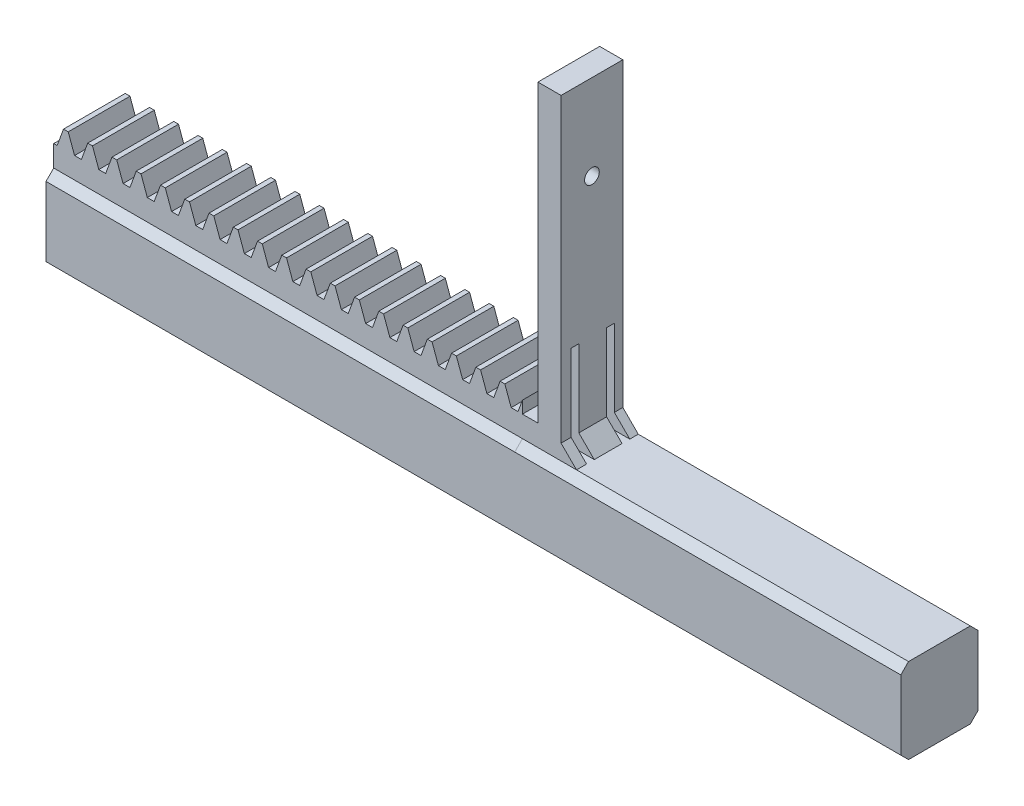
SolidWorks part; units mm, degrees
ref_plane "Front Plane" through (0, 0, 0) normal (0, 0, 1) x (1, 0, 0)
ref_plane "Top Plane" through (0, 0, 0) normal (0, 1, 0) x (1, 0, 0)
ref_plane "Right Plane" through (0, 0, 0) normal (1, 0, 0) x (0, 0, -1)
ref_plane "Plane1" through (0, 0, -3.7928) normal (0, 0, -1) x (-1, 0, 0)
sketch "Sketch1" plane through (0, 0, -3.7928) normal (0, 0, -1) x (-1, 0, 0)
  line L0 (23.517, -6.4086) -> (22.698, -8.6586)
  line L1 (22.698, -8.6586) -> (21.8092, -8.6586)
  line L2 (21.8092, -8.6586) -> (21.2359, -7.0836)
  line L3 (21.2359, -7.0836) -> (21.2359, -12.4086)
  line L4 (21.2359, -12.4086) -> (66.2359, -12.4086)
  line L5 (81.9439, -8.6586) -> (81.9439, -12.4086)
  line L6 (66.6803, -8.6586) -> (65.7915, -8.6586)
  line L7 (65.7915, -8.6586) -> (64.9725, -6.4086)
  line L8 (64.9725, -6.4086) -> (64.3577, -6.4086)
  line L9 (64.3577, -6.4086) -> (63.5387, -8.6586)
  line L10 (63.5387, -8.6586) -> (62.6499, -8.6586)
  line L11 (62.6499, -8.6586) -> (61.8309, -6.4086)
  line L12 (61.8309, -6.4086) -> (61.2161, -6.4086)
  line L13 (61.2161, -6.4086) -> (60.3971, -8.6586)
  line L14 (60.3971, -8.6586) -> (59.5083, -8.6586)
  line L15 (59.5083, -8.6586) -> (58.6893, -6.4086)
  line L16 (58.6893, -6.4086) -> (58.0745, -6.4086)
  line L17 (58.0745, -6.4086) -> (57.2555, -8.6586)
  line L18 (57.2555, -8.6586) -> (56.3667, -8.6586)
  line L19 (56.3667, -8.6586) -> (55.5477, -6.4086)
  line L20 (55.5477, -6.4086) -> (54.9329, -6.4086)
  line L21 (54.9329, -6.4086) -> (54.114, -8.6586)
  line L22 (54.114, -8.6586) -> (53.2251, -8.6586)
  line L23 (53.2251, -8.6586) -> (52.4062, -6.4086)
  line L24 (52.4062, -6.4086) -> (51.7913, -6.4086)
  line L25 (51.7913, -6.4086) -> (50.9724, -8.6586)
  line L26 (50.9724, -8.6586) -> (50.0835, -8.6586)
  line L27 (50.0835, -8.6586) -> (49.2646, -6.4086)
  line L28 (49.2646, -6.4086) -> (48.6497, -6.4086)
  line L29 (48.6497, -6.4086) -> (47.8308, -8.6586)
  line L30 (47.8308, -8.6586) -> (46.9419, -8.6586)
  line L31 (46.9419, -8.6586) -> (46.123, -6.4086)
  line L32 (46.123, -6.4086) -> (45.5081, -6.4086)
  line L33 (45.5081, -6.4086) -> (44.6892, -8.6586)
  line L34 (44.6892, -8.6586) -> (43.8003, -8.6586)
  line L35 (43.8003, -8.6586) -> (42.9814, -6.4086)
  line L36 (42.9814, -6.4086) -> (42.3665, -6.4086)
  line L37 (42.3665, -6.4086) -> (41.5476, -8.6586)
  line L38 (41.5476, -8.6586) -> (40.6587, -8.6586)
  line L39 (40.6587, -8.6586) -> (39.8398, -6.4086)
  line L40 (39.8398, -6.4086) -> (39.2249, -6.4086)
  line L41 (39.2249, -6.4086) -> (38.406, -8.6586)
  line L42 (38.406, -8.6586) -> (37.5171, -8.6586)
  line L43 (37.5171, -8.6586) -> (36.6982, -6.4086)
  line L44 (36.6982, -6.4086) -> (36.0833, -6.4086)
  line L45 (36.0833, -6.4086) -> (35.2644, -8.6586)
  line L46 (35.2644, -8.6586) -> (34.3755, -8.6586)
  line L47 (34.3755, -8.6586) -> (33.5566, -6.4086)
  line L48 (33.5566, -6.4086) -> (32.9417, -6.4086)
  line L49 (32.9417, -6.4086) -> (32.1228, -8.6586)
  line L50 (32.1228, -8.6586) -> (31.2339, -8.6586)
  line L51 (31.2339, -8.6586) -> (30.415, -6.4086)
  line L52 (30.415, -6.4086) -> (29.8001, -6.4086)
  line L53 (29.8001, -6.4086) -> (28.9812, -8.6586)
  line L54 (28.9812, -8.6586) -> (28.0923, -8.6586)
  line L55 (28.0923, -8.6586) -> (27.2734, -6.4086)
  line L56 (27.2734, -6.4086) -> (26.6586, -6.4086)
  line L57 (26.6586, -6.4086) -> (25.8396, -8.6586)
  line L58 (25.8396, -8.6586) -> (24.9508, -8.6586)
  line L59 (24.9508, -8.6586) -> (24.1318, -6.4086)
  line L60 (24.1318, -6.4086) -> (23.517, -6.4086)
  line L61 (81.4994, -8.6586) -> (81.9439, -8.6586)
  line L62 (80.6805, -6.4086) -> (81.4994, -8.6586)
  line L63 (80.0656, -6.4086) -> (80.6805, -6.4086)
  line L64 (79.2467, -8.6586) -> (80.0656, -6.4086)
  line L65 (78.3578, -8.6586) -> (79.2467, -8.6586)
  line L66 (77.5389, -6.4086) -> (78.3578, -8.6586)
  line L67 (76.924, -6.4086) -> (77.5389, -6.4086)
  line L68 (76.1051, -8.6586) -> (76.924, -6.4086)
  line L69 (75.2162, -8.6586) -> (76.1051, -8.6586)
  line L70 (74.3973, -6.4086) -> (75.2162, -8.6586)
  line L71 (73.7824, -6.4086) -> (74.3973, -6.4086)
  line L72 (72.9635, -8.6586) -> (73.7824, -6.4086)
  line L73 (72.0746, -8.6586) -> (72.9635, -8.6586)
  line L74 (71.2557, -6.4086) -> (72.0746, -8.6586)
  line L75 (70.6409, -6.4086) -> (71.2557, -6.4086)
  line L76 (69.8219, -8.6586) -> (70.6409, -6.4086)
  line L77 (68.933, -8.6586) -> (69.8219, -8.6586)
  line L78 (68.1141, -6.4086) -> (68.933, -8.6586)
  line L79 (67.4993, -6.4086) -> (68.1141, -6.4086)
  line L80 (66.6803, -8.6586) -> (67.4993, -6.4086)
  line L81 (66.2359, -12.4086) -> (81.9439, -12.4086)
extrude "Boss-Extrude1" add sketch "Sketch1" against normal blind 8
sketch "Sketch2" plane through (0, -12.4086, 0) normal (0, -1, 0) x (1, 0, 0)
  line L0 (-81.9439, 4.2072) -> (-81.9439, -3.7928) construction
  line L1 (-81.9439, 5.2072) -> (28.7641, 5.2072)
  line L2 (-81.9439, 5.2072) -> (-81.9439, -4.7928)
  line L3 (-81.9439, -4.7928) -> (28.7641, -4.7928)
  line L4 (28.7641, 5.2072) -> (28.7641, -4.7928)
  line L5 (-21.2359, 4.2072) -> (-21.2359, -3.7928) construction
  point P8 (-81.9439, 0.2072)
  dimension "D1" = 10
  dimension "D2" = 50
extrude "Boss-Extrude2" add sketch "Sketch2" along normal blind 10
chamfer "Chamfer1" distance 1 angle 45 1 edges at (-51.5899, -12.4086, 4.2072)
chamfer "Chamfer2" distance 1 angle 45 1 edges at (-51.5899, -12.4086, -3.7928)
sketch "Sketch3" plane through (0, -12.4086, 0) normal (0, 1, 0) x (1, 0, 0)
  line L1 (-21.2359, 3.7928) -> (28.7641, 3.7928)
  line L2 (-21.2359, 3.7928) -> (-21.2359, -4.2072)
  line L3 (-21.2359, -4.2072) -> (28.7641, -4.2072)
  line L4 (28.7641, 3.7928) -> (28.7641, -4.2072)
  line L6 (28.7641, 4.7928) -> (28.7641, -5.2072) construction
  dimension "D1" = 8
extrude "Boss-Extrude3" add sketch "Sketch3" along normal blind 1
chamfer "Chamfer3" distance 1 angle 45 1 edges at (3.7641, -12.4086, 4.2072)
chamfer "Chamfer4" distance 1 angle 45 1 edges at (3.7641, -12.4086, -3.7928)
sketch "Sketch4" plane through (0, -22.4086, 0) normal (0, -1, 0) x (1, 0, 0)
  line L1 (-19.2359, 4.2072) -> (-16.2359, 4.2072)
  line L2 (-19.2359, 4.2072) -> (-19.2359, -3.7928)
  line L3 (-19.2359, -3.7928) -> (-16.2359, -3.7928)
  line L4 (-16.2359, 4.2072) -> (-16.2359, -3.7928)
  line L8 (-81.9439, -4.7928) -> (28.7641, -4.7928) construction
  line L9 (28.7641, -4.7928) -> (28.7641, 5.2072) construction
  dimension "D1" = 48
  dimension "D2" = 3
  dimension "D3" = 8
  dimension "D4" = 1
extrude "Boss-Extrude6" add sketch "Sketch4" against normal blind 52
sketch "Sketch10" plane through (-16.2359, 0, 0) normal (1, 0, 0) x (0, 0, -1)
  line L0 (-4.2072, -11.4086) -> (3.7928, -11.4086) construction
  line L1 (-2.9072, 0.5914) -> (-1.9072, 0.5914)
  line L2 (-2.9072, 0.5914) -> (-2.9072, -11.4086)
  line L3 (-2.9072, -11.4086) -> (-1.9072, -11.4086)
  line L4 (-1.9072, 0.5914) -> (-1.9072, -11.4086)
  line L5 (3.7928, 29.5914) -> (3.7928, -11.4086) construction
  line L6 (1.6928, 0.5914) -> (2.6928, 0.5914)
  line L7 (1.6928, 0.5914) -> (1.6928, -11.4086)
  line L8 (1.6928, -11.4086) -> (2.6928, -11.4086)
  line L9 (2.6928, 0.5914) -> (2.6928, -11.4086)
  dimension "D1" = 1
  dimension "D2" = 1
  dimension "D3" = 3.6
  dimension "D4" = 1.1
  dimension "D5" = 12
  dimension "D6" = 12
extrude "Cut-Extrude4" cut sketch "Sketch10" against normal blind 4
sketch "Sketch12" plane through (-19.2359, 0, 0) normal (-1, 0, 0) x (0, 0, 1)
  line L2 (4.2072, 29.5914) -> (4.2072, -11.4086) construction
  line L3 (-1.6928, -11.4086) -> (1.9072, -11.4086) construction
  circle A0 centre (0.2072, 18.5414) radius 0.95
  dimension "D1" = 1.9
  dimension "D2" = 29
  dimension "D3" = 4
chamfer "Chamfer7" distance 2 angle 45 3 edges at (-16.2359, -11.4086, 0.1072) (-16.2359, -11.4086, -3.2428) (-16.2359, -11.4086, 3.5572)
extrude "Cut-Extrude5" cut sketch "Sketch12" against normal blind 4
chamfer "Chamfer8" distance 1 angle 45 2 edges at (-26.5899, -22.4086, 5.2072) (-26.5899, -22.4086, -4.7928)
sketch "Sketch13" plane through (0, -11.4086, 0) normal (0, 1, 0) x (1, 0, 0)
  line L1 (-21.2359, 3.7928) -> (-19.2359, 3.7928)
  line L2 (-21.2359, 3.7928) -> (-21.2359, -4.2072)
  line L3 (-21.2359, -4.2072) -> (-19.2359, -4.2072)
  line L4 (-19.2359, 3.7928) -> (-19.2359, -4.2072)
extrude "Boss-Extrude7" add sketch "Sketch13" along normal blind 2.75
